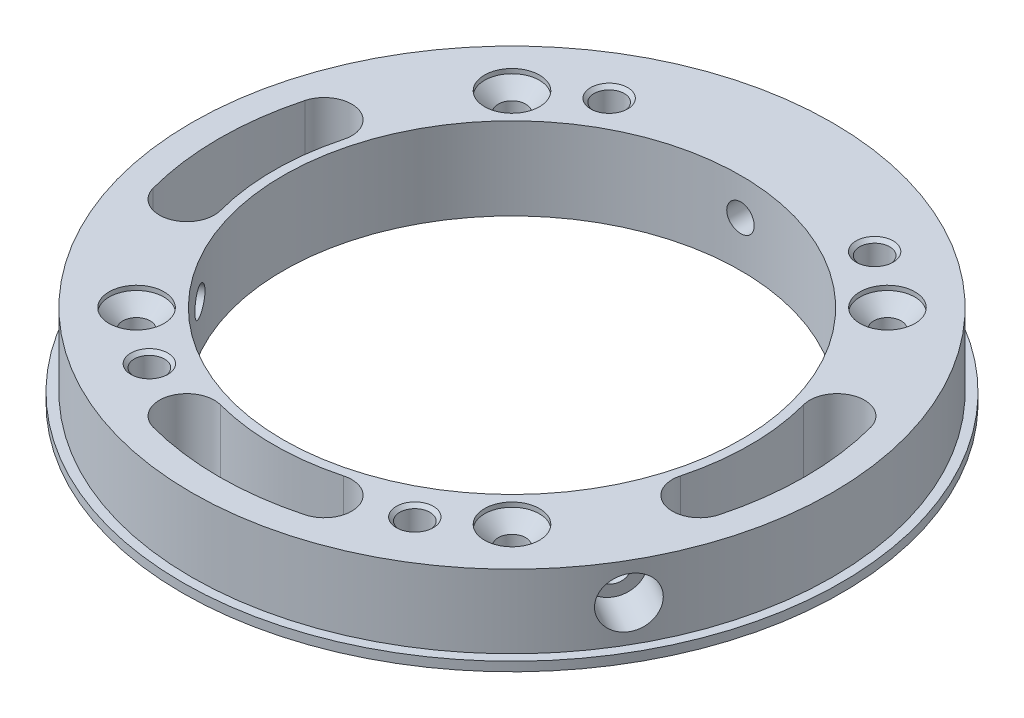
SolidWorks part; units mm, degrees
material "6061 合金"
ref_plane "前视基准面" through (0, 0, 0) normal (0, 0, 1) x (1, 0, 0)
ref_plane "上视基准面" through (0, 0, 0) normal (0, 1, 0) x (1, 0, 0)
ref_plane "右视基准面" through (0, 0, 0) normal (1, 0, 0) x (0, 0, -1)
sketch "草图5" plane through (0, 0, 0) normal (0, 1, 0) x (1, 0, 0)
  circle A0 centre (0, 0) radius 35
  circle A26 centre (0, 0) radius 25
  dimension "D1" = 70
  dimension "D2" = 50
extrude "凸台-拉伸1" add sketch "草图5" along normal blind 9
sketch "草图17" plane through (0, 0, 0) normal (0, -1, 0) x (1, 0, 0)
  circle A0 centre (0, 0) radius 36
  circle A1 centre (0, 0) radius 35 construction
  circle A2 centre (0, 0) radius 35
  dimension "D1" = 1
extrude "凸台-拉伸2" add sketch "草图17" against normal blind 1
sketch "草图2" plane through (0, 0, 6) normal (0, -1, 0) x (-1, 0, 0)
  circle A1 centre (0, 6) radius 25 construction
  arc A5 (-7.5058, 34.0118) -> (7.5058, 34.0118) centre (0, 6) cw construction
  arc A6 (8.2822, 36.9096) -> (-8.2822, 36.9096) centre (0, 6) ccw construction
  arc A7 (6.7293, 31.1141) -> (-6.7293, 31.1141) centre (0, 6) ccw construction
  arc A8 (6.7293, 31.1141) -> (8.2822, 36.9096) centre (7.5058, 34.0118) ccw construction
  arc A9 (-8.2822, 36.9096) -> (-6.7293, 31.1141) centre (-7.5058, 34.0118) ccw construction
  arc A15 (28.0118, 13.5058) -> (28.0118, -1.5058) centre (0, 6) cw construction
  arc A42 (30.9096, -2.2822) -> (30.9096, 14.2822) centre (0, 6) ccw
  arc A43 (25.1141, -0.7293) -> (25.1141, 12.7293) centre (0, 6) ccw
  arc A44 (25.1141, -0.7293) -> (30.9096, -2.2822) centre (28.0118, -1.5058) ccw
  arc A45 (30.9096, 14.2822) -> (25.1141, 12.7293) centre (28.0118, 13.5058) ccw
  arc A46 (7.5058, -22.0118) -> (-7.5058, -22.0118) centre (0, 6) cw construction
  arc A47 (-8.2822, -24.9096) -> (8.2822, -24.9096) centre (0, 6) ccw
  arc A48 (-6.7293, -19.1141) -> (6.7293, -19.1141) centre (0, 6) ccw
  arc A49 (-6.7293, -19.1141) -> (-8.2822, -24.9096) centre (-7.5058, -22.0118) ccw
  arc A50 (8.2822, -24.9096) -> (6.7293, -19.1141) centre (7.5058, -22.0118) ccw
  arc A51 (-28.0118, -1.5058) -> (-28.0118, 13.5058) centre (0, 6) cw construction
  arc A52 (-30.9096, 14.2822) -> (-30.9096, -2.2822) centre (0, 6) ccw
  arc A53 (-25.1141, 12.7293) -> (-25.1141, -0.7293) centre (0, 6) ccw
  arc A54 (-25.1141, 12.7293) -> (-30.9096, 14.2822) centre (-28.0118, 13.5058) ccw
  arc A55 (-30.9096, -2.2822) -> (-25.1141, -0.7293) centre (-28.0118, -1.5058) ccw
  circle A56 centre (0, 6) radius 29 construction
  circle A57 centre (20.5061, 26.5061) radius 1.5
  circle A58 centre (20.5061, -14.5061) radius 1.5
  circle A59 centre (-20.5061, -14.5061) radius 1.5
  circle A60 centre (-20.5061, 26.5061) radius 1.5
  circle A61 centre (0, 6) radius 35 construction
  point P13 (0, 35)
  point P18 (29, 6)
  point P27 (0, -23)
  point P36 (-29, 6)
  dimension "D1" = 58
  dimension "D2" = 3
  dimension "D3" = 1
  dimension "D4" = 3
  dimension "D5" = 30
  dimension "D6" = 4
extrude "切除-拉伸1" cut sketch "草图2" against normal through all
hole_wizard "M4 螺纹孔4" positions "草图12" profile "草图13" tap size "M4" standard "GB" end condition through all
sketch "草图12" plane through (0, 9, 0) normal (0, 1, 0) x (1, 0, 0)
  line L0 (-20.5061, 20.5061) -> (0, 0) construction
  line L1 (0, 0) -> (-14.5, 25.1147) construction
  line L5 (0, 0) -> (0, 33.6072) construction
  circle A0 centre (0, 0) radius 29 construction
  point P0 (-14.5, 25.1147)
  point P32 (14.5, 25.1147)
  point P34 (14.5, -25.1147)
  point P35 (-14.5, -25.1147)
  point P47 (-29, 0) [skipped]
  point P48 (29, 0) [skipped]
  dimension "D1" = 30
  dimension "D2" = 45
  dimension "D3" = 6
sketch "草图13" plane through (-14.5, 9, -25.1147) normal (1, 0, 0) x (0, 0, 1)
  line L0 (0, 0) -> (0, 9)
  line L1 (0, 9) -> (1.65, 9)
  line L2 (1.65, 9) -> (1.65, 0.375)
  line L3 (1.65, 0.375) -> (2.025, 0)
  line L5 (2.025, 0) -> (0, 0)
  line L6 (-1.65, 0.375) -> (-2.025, 0) construction
  line L11 (0, -6.35) -> (0, 107.95) construction
  dimension "通孔螺纹孔钻头直径" = 3.3
  dimension "通孔螺纹孔钻头深度" = 9
  dimension "近端锥形沉头孔直径" = 4.05
  dimension "近端锥形沉头孔角度" = 90
cosmetic thread "孔螺蚊线21" parameters "D2"=4
cosmetic thread "孔螺蚊线23" parameters "D2"=4
cosmetic thread "孔螺蚊线24" parameters "D2"=4
cosmetic thread "孔螺蚊线25" parameters "D2"=4
hole_wizard "孔1" positions "草图14" profile "草图15" legacy end condition through all
sketch "草图14" plane through (0, 9, 0) normal (0, 1, 0) x (1, 0, 0)
  point P0 (-20.5061, -20.5061)
  point P3 (20.5061, -20.5061)
  point P6 (20.5061, 20.5061)
  point P9 (-20.5061, 20.5061)
sketch "草图15" plane through (-20.5061, 9, 20.5061) normal (1, 0, 0) x (0, 0, 1)
  line L0 (0, 0) -> (0, 9)
  line L1 (0, 9) -> (1.5, 9)
  line L2 (1.5, 9) -> (1.5, 2)
  line L3 (1.5, 2) -> (3, 0.5)
  line L4 (3, 0.5) -> (3, 0)
  line L5 (3, 0) -> (0, 0)
  line L6 (0, -6.13) -> (0, 109.2824) construction
  line L7 (-1.5, 2) -> (-3, 0.5) construction
  line L8 (0, 9) -> (-1.5, 9) construction
  dimension "直径" = 3
  dimension "深度" = 9
  dimension "沉头坑直径" = 6
  dimension "沉头坑深度" = 0.5
  dimension "导头角度" = 90
sketch "草图18" plane through (0, 0, 0) normal (0, 0, 1) x (1, 0, 0)
  line L0 (0, 1) -> (0, 9) construction
  line L1 (36, 1) -> (-36, 1) construction
  line L2 (25, 9) -> (-25, 9) construction
  circle A0 centre (0, 5) radius 1.5
  dimension "D1" = 3
extrude "切除-拉伸2" cut sketch "草图18" against normal blind 30.2
sketch "草图19" plane through (0, 0, -30.2) normal (0, 0, 1) x (1, 0, 0)
  circle A0 centre (0, 5) radius 2.75
  dimension "D1" = 5.5
extrude "切除-拉伸3" cut sketch "草图19" against normal through all
pattern_circular "阵列(圆周)1" count 3 over 360 about axis through (0, 9, 0) along (0, -1, 0) of "切除-拉伸2", "切除-拉伸3"
chamfer "倒角1" distance 1 angle 45 12 edges at (-32, 0, 0) (-27.2354, 0, -10.4035) (-27.2354, 0, 10.4035) (-26, 0, 0) (32, 0, 0) (27.2354, 0, 10.4035) (27.2354, 0, -10.4035) (26, 0, 0) (-10.4035, 0, 27.2354) (0, 0, 26) (0, 0, 32) (10.4035, 0, 27.2354)
